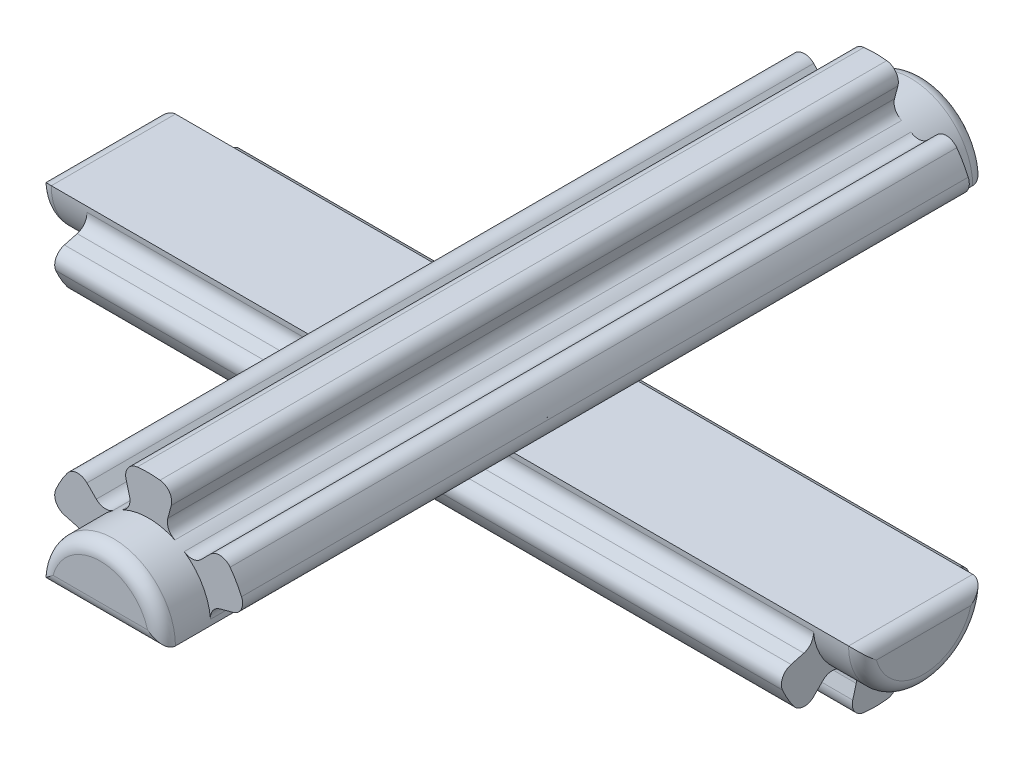
SolidWorks part; units mm, degrees
ref_plane "Front Plane" through (0, 0, 0) normal (0, 0, 1) x (1, 0, 0)
ref_plane "Top Plane" through (0, 0, 0) normal (0, 1, 0) x (1, 0, 0)
ref_plane "Right Plane" through (0, 0, 0) normal (1, 0, 0) x (0, 0, -1)
sketch "Sketch10" plane through (13.9, 0, 0) normal (1, 0, 0) x (0, 0, -1)
  line L0 (-2.375, 0) -> (2.375, 0)
  line L1 (-2.2941, -0.6147) -> (-3.743, -1.0029)
  line L2 (2.2941, -0.6147) -> (3.743, -1.0029)
  line L3 (-1.6794, -1.6794) -> (-2.74, -2.74)
  line L4 (1.6794, -1.6794) -> (2.74, -2.74)
  line L5 (-0.6147, -2.2941) -> (-1.0029, -3.743)
  line L6 (0.6147, -2.2941) -> (1.0029, -3.743)
  arc A0 (-3.743, -1.0029) -> (-2.74, -2.74) centre (0, 0) ccw
  arc A1 (-2.375, 0) -> (-2.2941, -0.6147) centre (0, 0) ccw
  arc A2 (2.2941, -0.6147) -> (2.375, 0) centre (0, 0) ccw
  arc A3 (0.6147, -2.2941) -> (1.6794, -1.6794) centre (0, 0) ccw
  arc A4 (-1.6794, -1.6794) -> (-0.6147, -2.2941) centre (0, 0) ccw
  arc A5 (-1.0029, -3.743) -> (1.0029, -3.743) centre (0, 0) ccw
  arc A6 (2.74, -2.74) -> (3.743, -1.0029) centre (0, 0) ccw
  arc A7 (-2.375, 0) -> (2.375, 0) centre (0, 0) ccw
  dimension "D1" = 3.875
  dimension "D2" = 2.375
  dimension "D5" = 15
  dimension "D6" = 15
  dimension "D7" = 30
  dimension "D8" = 30
extrude "Boss-Extrude9" add sketch "Sketch10" against normal blind 31.5 from offset 1.85 contours A1 A7 A4 A3 A2 L0 region at (13.9, -1.008, 0)
extrude "Boss-Extrude10" add sketch "Sketch10<3>" against normal blind 27.8 contours A7 L4 A6 L2 | A7 L5 A5 L6 | A7 L1 A0 L3 region at (13.9, -1.5744, 2.7269) region at (13.9, -1.5744, -2.7269) region at (13.9, -3.1487, 0)
sketch "Sketch10<3>" plane through (13.9, 0, 0) normal (1, 0, 0) x (0, 0, -1) same geometry as "Sketch10"
fillet "Fillet4" radius 0.5 16 edges at (-15.75, 0, 0) (-15.75, -2.375, 0) (15.75, 0, 0) (15.75, -2.375, 0) (0, -0.6147, -2.2941) (0, -1.0029, -3.743) (0, -2.74, -2.74) (0, -1.6794, -1.6794) (0, -2.2941, -0.6147) (0, -3.743, -1.0029) (0, -3.743, 1.0029) (0, -2.2941, 0.6147) (0, -1.6794, 1.6794) (0, -2.74, 2.74) (0, -0.6147, 2.2941) (0, -1.0029, 3.743)
ref_plane "Plane2" through (0, 0, 15.75) normal (0, 0, 1) x (1, 0, 0)
sketch "Sketch12" plane through (0, 0, 15.75) normal (0, 0, 1) x (1, 0, 0)
  line L0 (-2.375, 0) -> (2.375, 0)
  line L1 (-2.2941, 0.6147) -> (-3.743, 1.0029)
  line L3 (-0.6147, 2.2941) -> (-1.0029, 3.743)
  line L4 (0.6147, 2.2941) -> (1.0029, 3.743)
  line L5 (2.2941, 0.6147) -> (3.743, 1.0029)
  line L6 (1.6794, 1.6794) -> (2.74, 2.74)
  line L7 (-1.6794, 1.6794) -> (-2.74, 2.74)
  arc A0 (2.375, 0) -> (2.2941, 0.6147) centre (0, 0) ccw
  arc A1 (3.743, 1.0029) -> (2.74, 2.74) centre (0, 0) ccw
  arc A2 (-0.6147, 2.2941) -> (-1.6794, 1.6794) centre (0, 0) ccw
  arc A3 (-2.2941, 0.6147) -> (-2.375, 0) centre (0, 0) ccw
  arc A4 (1.6794, 1.6794) -> (0.6147, 2.2941) centre (0, 0) ccw
  arc A5 (1.0029, 3.743) -> (-1.0029, 3.743) centre (0, 0) ccw
  arc A6 (-2.74, 2.74) -> (-3.743, 1.0029) centre (0, 0) ccw
  arc A7 (2.2941, 0.6147) -> (-2.2941, 0.6147) centre (0, 0) ccw
  dimension "D1" = 2.375
  dimension "D2" = 3.875
extrude "Boss-Extrude11" add sketch "Sketch12" against normal blind 31.5 separate body contours A0 A7 A4 A2 A3 L0 region at (0, 1.008, 15.75)
extrude "Boss-Extrude12" add sketch "Sketch12<3>" against normal blind 27.8 from offset 1.85 contours A7 L7 A6 L1 | A7 L4 A5 L3 | A7 L5 A1 L6 region at (-2.7269, 1.5744, 15.75) region at (2.7269, 1.5744, 15.75) region at (0, 3.1487, 15.75) offset against normal yes
sketch "Sketch12<3>" plane through (0, 0, 15.75) normal (0, 0, 1) x (1, 0, 0) same geometry as "Sketch12"
fillet "Fillet5" radius 0.5 16 edges at (0, 0, -15.75) (0, 2.375, -15.75) (0, 2.375, 15.75) (0, 0, 15.75) (2.2941, 0.6147, 0) (3.743, 1.0029, 0) (2.74, 2.74, 0) (1.6794, 1.6794, 0) (0.6147, 2.2941, 0) (1.0029, 3.743, 0) (-1.0029, 3.743, 0) (-0.6147, 2.2941, 0) (-2.74, 2.74, 0) (-1.6794, 1.6794, 0) (-2.2941, 0.6147, 0) (-3.743, 1.0029, 0)
